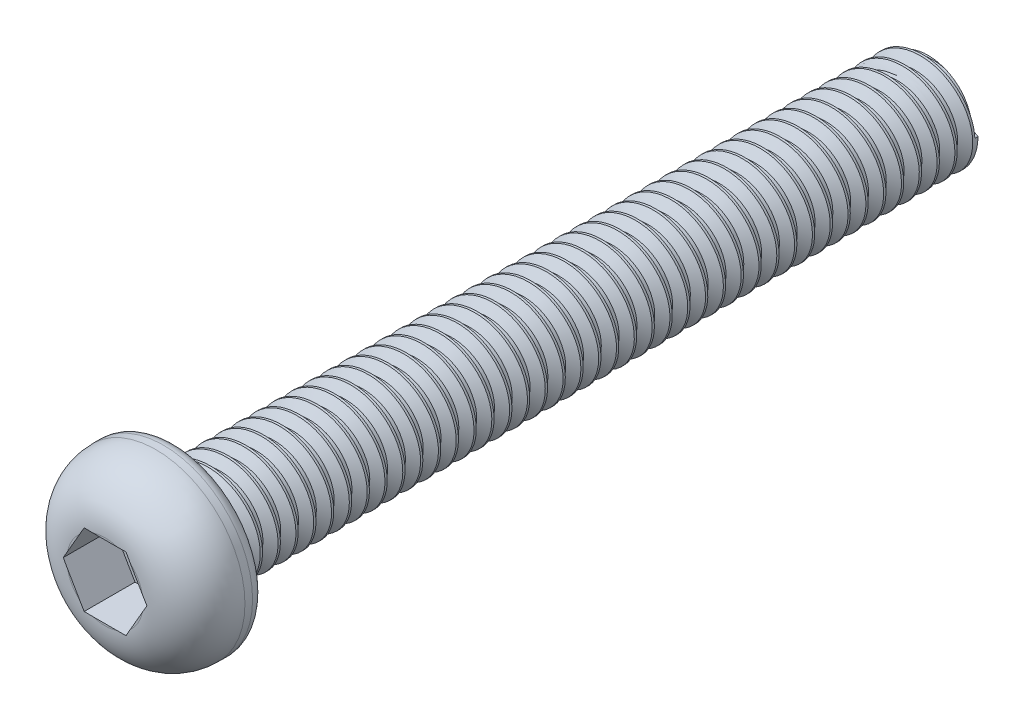
SolidWorks part; units mm, degrees
ref_plane "Front Plane" through (0, 0, 0) normal (0, 0, 1) x (1, 0, 0)
ref_plane "Top Plane" through (0, 0, 0) normal (0, 1, 0) x (1, 0, 0)
ref_plane "Right Plane" through (0, 0, 0) normal (1, 0, 0) x (0, 0, -1)
sketch "Sketch1" plane through (0, 0, 0) normal (0, 0, 1) x (1, 0, 0)
  circle A0 centre (0, 0) radius 2
  dimension "D1" = 4
extrude "Boss-Extrude1" add sketch "Sketch1" along normal blind 30
sketch "Sketch2" plane through (0, 0, 30) normal (0, 0, 1) x (1, 0, 0)
  circle A0 centre (0, 0) radius 3.5
  dimension "D1" = 7
extrude "Boss-Extrude2" add sketch "Sketch2" along normal blind 2.8
fillet "Fillet1" radius 2 1 edges at (3.5, 0, 32.8)
fillet "Fillet2" radius 0.5 1 edges at (3.5, 0, 30)
sketch "Sketch3" plane through (0, 0, 32.8) normal (0, 0, 1) x (1, 0, 0)
  line L1 (1.6437, 0) -> (0.8219, 1.4235)
  line L2 (0.8219, 1.4235) -> (-0.8219, 1.4235)
  line L3 (-0.8219, 1.4235) -> (-1.6437, 0)
  line L4 (-1.6437, 0) -> (-0.8219, -1.4235)
  line L5 (-0.8219, -1.4235) -> (0.8219, -1.4235)
  line L6 (0.8219, -1.4235) -> (1.6437, 0)
  circle A0 centre (0, 0) radius 1.4235 construction
extrude "Cut-Extrude1" cut sketch "Sketch3" against normal blind 2
thread "Thread1" pitch 0.7 profile "Thread Profile1" start angle 0, offset 0, length 29.6, pitch 0.7, diameter 4
ref_plane "Plane4" through (2, 0, 0) normal (0, -1, 0) x (1, 0, 0)
sketch "Thread Profile1" plane through (2, 0, 0) normal (0, -1, 0) x (1, 0, 0)
  line L0 (0, 0) -> (0, 0.7) construction
  line L11 (0, 0) -> (0, 0.6125)
  line L12 (0, 0.6125) -> (-0.3789, 0.3937)
  line L13 (-0.3789, 0.3937) -> (-0.3789, 0.2187)
  line L15 (-0.3789, 0.2187) -> (0, 0)
  line L17 (-0.3789, 0.3062) -> (0, 0.3062) construction
  point P2 (0, 0)
  dimension "Pitch" = 0.7
  dimension "Profile_Angle" = 60
  dimension "Profile_Land" = 0.175
  dimension "Profile_Height" = 0.3789
ref_axis "Axis1" through (0, 0, 30.0056) along (0, 0, -1)
sketch "Sketch4" plane through (0, 0, 0) normal (0, 1, 0) x (1, 0, 0)
  line L0 (-0.6296, 0) -> (-2.4277, -0.6437)
  line L1 (2, 0) -> (-2, 0) construction
  line L2 (-2.4277, -0.6437) -> (-2.4277, 0.5435)
  line L3 (-2.4277, 0.5435) -> (-0.6296, 0.5435)
  line L4 (-0.6296, 0.5435) -> (-0.6296, 0)
revolve "Cut-Revolve2" cut sketch "Sketch4" angle 360 about axis through (0, 0, 30.0056) along (0, 0, -1)
